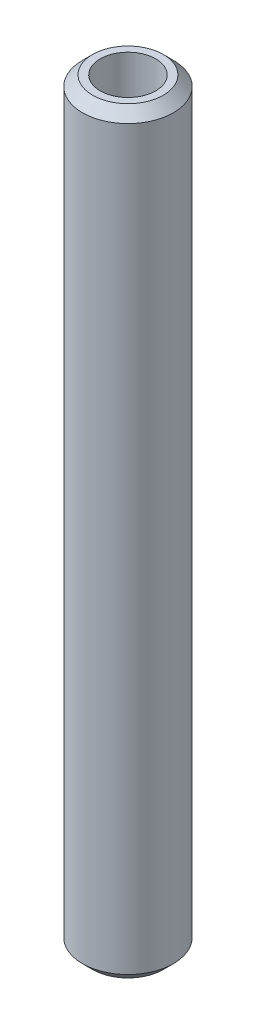
SolidWorks part; units mm, degrees
ref_plane "Front Plane" through (0, 0, 0) normal (0, 0, 1) x (1, 0, 0)
ref_plane "Top Plane" through (0, 0, 0) normal (0, 1, 0) x (1, 0, 0)
ref_plane "Right Plane" through (0, 0, 0) normal (1, 0, 0) x (0, 0, -1)
sketch "Sketch1" plane through (0, 0, 0) normal (0, 1, 0) x (1, 0, 0)
  circle A0 centre (0, 0) radius 12.5
  dimension "SHAFT_OD" = 25
extrude "Boss-Extrude1" add sketch "Sketch1" along normal blind 208.252
sketch "Sketch2" plane through (0, 0, 0) normal (0, 1, 0) x (1, 0, 0)
  circle A0 centre (0, 0) radius 7.6389
  dimension "BORE_D" = 15.2779
extrude "Cut-Extrude1" cut sketch "Sketch2" along normal through all
chamfer "Chamfer1" distance 2.7822 angle 45 2 edges at (0, 208.252, 12.5) (0, 0, 12.5)
